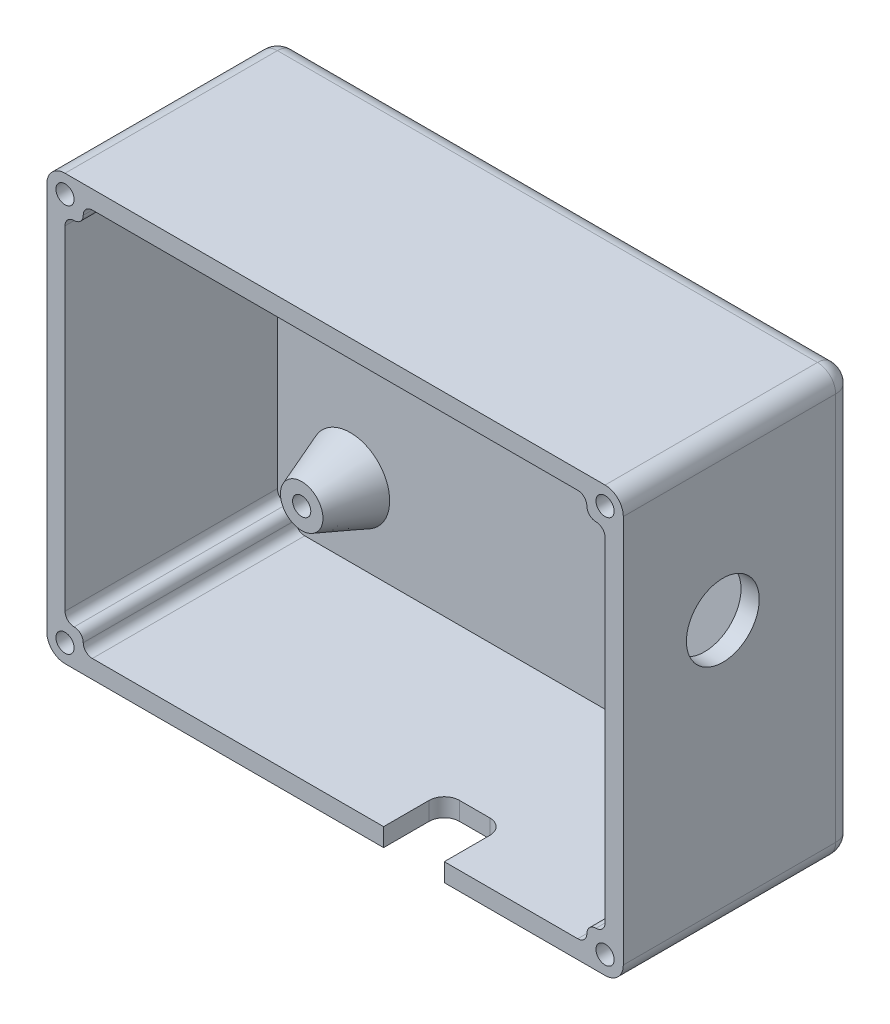
SolidWorks part; units mm, degrees
ref_plane "正面" through (0, 0, 0) normal (0, 0, 1) x (1, 0, 0)
ref_plane "平面" through (0, 0, 0) normal (0, 1, 0) x (1, 0, 0)
ref_plane "右側面" through (0, 0, 0) normal (1, 0, 0) x (0, 0, -1)
sketch "ｽｹｯﾁ1" plane through (0, 0, 0) normal (0, 0, 1) x (1, 0, 0)
  line L1 (0, 0) -> (95, 0)
  line L2 (0, 0) -> (0, 70)
  line L3 (0, 70) -> (95, 70)
  line L4 (95, 0) -> (95, 70)
  line L5 (0, 0) -> (95, 70) construction
  line L6 (0, 70) -> (95, 0) construction
  point P4 (47.5, 35)
  dimension "D1" = 70
  dimension "D2" = 95
extrude "ﾎﾞｽ - 押し出し1" add sketch "ｽｹｯﾁ1" along normal blind 3
sketch "ｽｹｯﾁ2" plane through (0, 0, 3) normal (0, 0, 1) x (1, 0, 0)
  line L1 (15, 55) -> (80, 55) construction
  line L2 (15, 55) -> (15, 15) construction
  line L3 (15, 15) -> (80, 15) construction
  line L4 (80, 55) -> (80, 15) construction
  line L5 (15, 55) -> (80, 15) construction
  line L6 (15, 15) -> (80, 55) construction
  line L7 (0, 70) -> (0, 0) construction
  line L8 (0, 35) -> (95, 35) construction
  line L9 (95, 0) -> (95, 70) construction
  circle A0 centre (15, 55) radius 3.5
  circle A1 centre (15, 15) radius 3.5
  circle A2 centre (80, 55) radius 3.5
  circle A3 centre (80, 15) radius 3.5
  point P4 (47.5, 35)
  dimension "D4" = 7
  dimension "D5" = 7
  dimension "D6" = 7
  dimension "D7" = 7
  dimension "D1" = 40
  dimension "D2" = 65
  dimension "D3" = 15
extrude "ﾎﾞｽ - 押し出し2" add sketch "ｽｹｯﾁ2" along normal blind 8
sketch "ｽｹｯﾁ3" plane through (0, 0, 11) normal (0, 0, 1) x (1, 0, 0)
  circle A4 centre (15, 55) radius 1.5
  circle A5 centre (80, 55) radius 1.5
  circle A6 centre (15, 15) radius 1.5
  circle A7 centre (80, 15) radius 1.5
  dimension "D1" = 3
  dimension "D2" = 3
  dimension "D3" = 3
  dimension "D4" = 3
extrude "ｶｯﾄ - 押し出し1" cut sketch "ｽｹｯﾁ3" against normal blind 8
chamfer "面取り1" [suppressed] distance 3 angle 69
chamfer "面取り2" distance 3 distance2 8 4 edges at (76.5, 15, 3) (76.5, 55, 3) (11.5, 55, 3) (11.5, 15, 3) first distance on face at (76.5, 15, 3)
sketch "ｽｹｯﾁ6" plane through (0, 0, 3) normal (0, 0, 1) x (1, 0, 0)
  line L14 (3, 3) -> (92, 3)
  line L15 (92, 3) -> (92, 67)
  line L16 (92, 67) -> (3, 67)
  line L17 (3, 67) -> (3, 3)
  line L18 (3, 3) -> (92, 3)
  line L19 (92, 3) -> (92, 67)
  line L20 (92, 67) -> (3, 67)
  line L21 (3, 67) -> (3, 3)
  line L22 (0, 70) -> (0, 0)
  line L23 (0, 0) -> (95, 0)
  line L24 (95, 0) -> (95, 70)
  line L25 (95, 70) -> (0, 70)
  line L26 (0, 70) -> (0, 0)
  line L27 (0, 0) -> (95, 0)
  line L28 (95, 0) -> (95, 70)
  line L29 (95, 70) -> (0, 70)
  dimension "D1" = 3
  dimension "D2" = 0
extrude "ﾎﾞｽ - 押し出し3" add sketch "ｽｹｯﾁ6" along normal blind 35 contours L26 L27 L28 L29 | L18 L19 L20 L21
sketch "ｽｹｯﾁ8" plane through (0, 0, 38) normal (0, 0, 1) x (1, 0, 0)
  line L1 (0, 70) -> (6, 70)
  line L2 (0, 70) -> (0, 64)
  line L3 (0, 64) -> (6, 64)
  line L4 (6, 70) -> (6, 64)
  line L5 (0, 70) -> (6, 64) construction
  line L6 (0, 64) -> (6, 70) construction
  line L7 (95, 70) -> (89, 70)
  line L8 (95, 70) -> (95, 64)
  line L9 (95, 64) -> (89, 64)
  line L10 (89, 70) -> (89, 64)
  line L11 (95, 70) -> (89, 64) construction
  line L12 (95, 64) -> (89, 70) construction
  line L13 (0, 0) -> (6, 0)
  line L14 (0, 0) -> (0, 6)
  line L15 (0, 6) -> (6, 6)
  line L16 (6, 0) -> (6, 6)
  line L17 (0, 0) -> (6, 6) construction
  line L18 (0, 6) -> (6, 0) construction
  line L19 (95, 0) -> (89, 0)
  line L20 (95, 0) -> (95, 6)
  line L21 (95, 6) -> (89, 6)
  line L22 (89, 0) -> (89, 6)
  line L23 (95, 0) -> (89, 6) construction
  line L24 (95, 6) -> (89, 0) construction
  point P4 (3, 67)
  point P10 (92, 67)
  point P16 (3, 3)
  point P22 (92, 3)
  dimension "D1" = 6
  dimension "D2" = 6
  dimension "D3" = 6
  dimension "D4" = 6
  dimension "D5" = 6
  dimension "D6" = 6
  dimension "D7" = 6
  dimension "D8" = 6
extrude "ﾎﾞｽ - 押し出し4" add sketch "ｽｹｯﾁ8" along direction (0, 0, -1) on the side against the normal up to next (35 mm away)
fillet "ﾌｨﾚｯﾄ4" radius 1.5 12 edges at (92, 6, 20.5) (89, 6, 20.5) (89, 3, 20.5) (6, 3, 20.5) (6, 6, 20.5) (3, 6, 20.5) (92, 64, 20.5) (89, 64, 20.5) (89, 67, 20.5) (6, 64, 20.5) (6, 67, 20.5) (3, 64, 20.5)
sketch "ｽｹｯﾁ10" plane through (0, 0, 38) normal (0, 0, 1) x (1, 0, 0)
  line L0 (0, 70) -> (0, 0) construction
  line L1 (95, 70) -> (0, 70) construction
  line L2 (95, 0) -> (95, 70) construction
  line L3 (0, 0) -> (95, 0) construction
  circle A0 centre (3, 67) radius 1.5
  circle A1 centre (92, 67) radius 1.5
  circle A2 centre (3, 3) radius 1.5
  circle A3 centre (92, 3) radius 1.5
  dimension "D1" = 3
  dimension "D2" = 3
  dimension "D3" = 3
  dimension "D4" = 3
  dimension "D5" = 3
  dimension "D6" = 3
  dimension "D7" = 3
  dimension "D8" = 3
  dimension "D9" = 3
  dimension "D10" = 3
  dimension "D11" = 3
  dimension "D12" = 3
extrude "ｶｯﾄ - 押し出し2" cut sketch "ｽｹｯﾁ10" against normal blind 15
fillet "ﾌｨﾚｯﾄ6" radius 3 4 edges at (0, 0, 19) (95, 0, 19) (95, 70, 19) (0, 70, 19)
sketch "ｽｹｯﾁ11" plane through (95, 0, 0) normal (1, 0, 0) x (0, 0, -1)
  line L0 (-12.6, 58.5) -> (-12.6, 11.5) construction
  line L1 (-12.6, 58.5) -> (-12.6, 11.5) construction
  line L2 (-12.6, 44) -> (-21.6, 44) construction
  circle A0 centre (-21.6, 44) radius 6
  dimension "D3" = 12
  dimension "D1" = 9
  dimension "D2" = 14.5
extrude "ｶｯﾄ - 押し出し3" cut sketch "ｽｹｯﾁ11" against normal blind 15
sketch "ｽｹｯﾁ12" plane through (0, 0, 0) normal (0, -1, 0) x (1, 0, 0)
  line L0 (83.5, 12.6) -> (11.5, 12.6) construction
  line L1 (83.5, 12.6) -> (11.5, 12.6) construction
  line L2 (3, 38) -> (92, 38) construction
  line L3 (65.5, 38) -> (55.5, 38)
  line L4 (65.5, 38) -> (65.5, 28)
  line L5 (65.5, 28) -> (55.5, 28)
  line L6 (55.5, 38) -> (55.5, 28)
  line L7 (65.5, 38) -> (55.5, 28) construction
  line L8 (65.5, 28) -> (55.5, 38) construction
  point P6 (60.5, 33)
  dimension "D1" = 0
  dimension "D2" = 10
  dimension "D3" = 18
  dimension "D4" = 10
extrude "ｶｯﾄ - 押し出し4" cut sketch "ｽｹｯﾁ12" against normal blind 15
fillet "ﾌｨﾚｯﾄ9" radius 2.5 2 edges at (55.5, 1.5, 28) (65.5, 1.5, 28)
fillet "ﾌｨﾚｯﾄ10" radius 3 8 edges at (94.1213, 69.1213, 0) (95, 35, 0) (94.1213, 0.8787, 0) (47.5, 0, 0) (0.8787, 0.8787, 0) (0, 35, 0) (0.8787, 69.1213, 0) (47.5, 70, 0)
